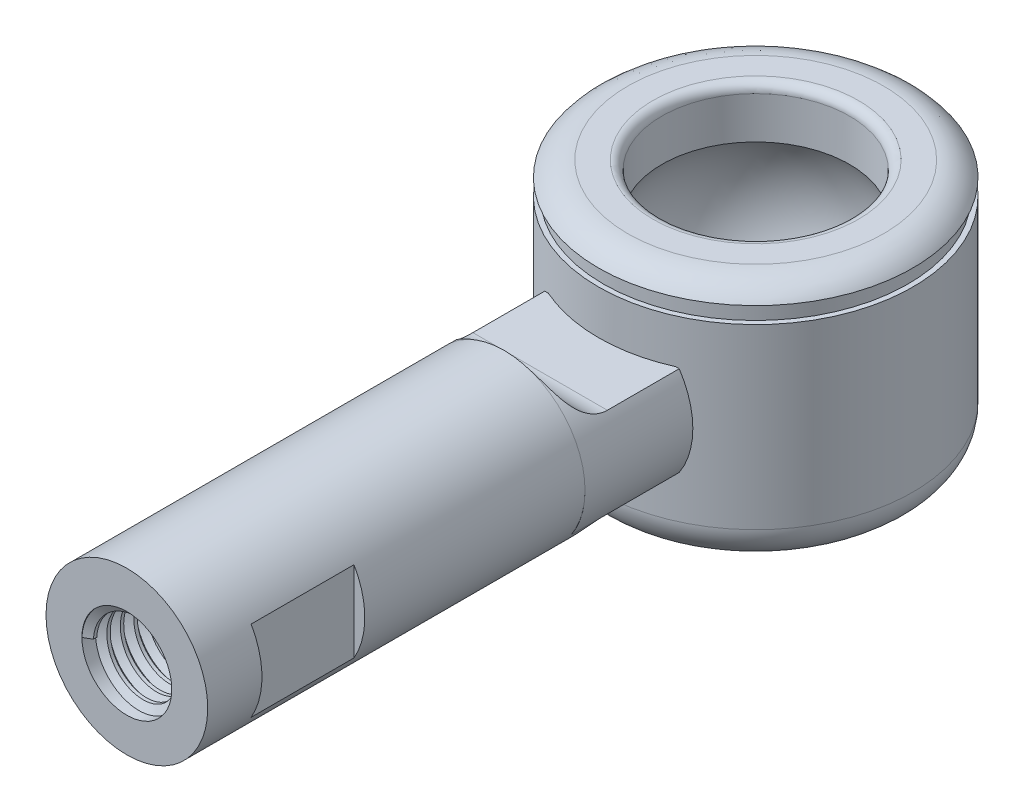
SolidWorks part; units mm, degrees
ref_plane "Front Plane" through (0, 0, 0) normal (0, 0, 1) x (1, 0, 0)
ref_plane "Top Plane" through (0, 0, 0) normal (0, 1, 0) x (1, 0, 0)
ref_plane "Right Plane" through (0, 0, 0) normal (1, 0, 0) x (0, 0, -1)
sketch "Sketch1" plane through (0, 0, 0) normal (0, 0, 1) x (1, 0, 0)
  line L0 (0, 1.3478) -> (0, 1.9842)
  line L1 (10.4493, 27) -> (17.5, 27)
  line L2 (17.5, 27) -> (17.5, 25.3212)
  line L3 (17.5, 0) -> (14.9786, 0)
  line L4 (14.9786, 0) -> (14.9786, 1.3478)
  line L5 (14.9786, 1.3478) -> (0, 1.3478)
  line L6 (0, 26.9842) -> (0, 27)
  line L7 (0, 26.9842) -> (0, 1.3478) construction
  line L10 (17.5, 23.4945) -> (17.5, 0)
  line L11 (17.5, 25.3212) -> (16.9454, 25.3212)
  line L13 (17.5, 23.4945) -> (16.9454, 23.4945)
  line L14 (16.9454, 25.3212) -> (16.9454, 23.4945)
  line L16 (10.4493, 27) -> (10.4493, 21.3443)
  arc A0 (10.4493, 21.3443) -> (0, 1.9842) centre (0, 14.4842) cw
  dimension "D3" = 12.5
  dimension "D2" = 17.5
  dimension "D4" = 1.3478
revolve "Revolve1" add sketch "Sketch1" angle 360 about L7 region at (13.4063, 12.4205, 0)
fillet "Fillet1" radius 4 2 edges at (0, 0, 17.5) (0, 27, 17.5)
ref_plane "Plane1" through (0, 0, 16) normal (0, 0, 1) x (1, 0, 0)
sketch "Sketch2" plane through (0, 0, 16) normal (0, 0, 1) x (1, 0, 0)
  line L0 (0, 23.4945) -> (0, 3.7167)
  line L1 (-7.4833, 18.6056) -> (7.4833, 18.6056)
  line L3 (-7.4833, 8.6056) -> (7.4833, 8.6056)
  line L5 (17.5, 23.4945) -> (-17.5, 23.4945) construction
  line L6 (-17.5, 3.7167) -> (17.5, 3.7167) construction
  arc A0 (-7.4833, 18.6056) -> (-7.4833, 8.6056) centre (0, 13.6056) ccw
  arc A1 (7.4833, 8.6056) -> (7.4833, 18.6056) centre (0, 13.6056) ccw
  point P12 (0, 18.6056)
  dimension "D2" = 18
  dimension "D1" = 10
  dimension "D3" = 5
extrude "Boss-Extrude1" add sketch "Sketch2" along normal blind 12 contours L1 A0 L3 L0 | L3 A1 L1 L0 region at (4.2681, 13.6056, 16) region at (-4.2681, 13.6056, 16)
sketch "Sketch3" plane through (0, 0, 28) normal (0, 0, 1) x (1, 0, 0)
  line L0 (0, 3.7167) -> (0, 23.4945) construction
  circle A0 centre (0, 13.6369) radius 9
  dimension "D1" = 18
extrude "Boss-Extrude2" add sketch "Sketch3" along normal blind 42
fillet "Fillet4" radius 4 2 edges at (0, 8.6056, 28) (0, 18.6056, 28)
sketch "Sketch4" plane through (0, 0, 70) normal (0, 0, 1) x (1, 0, 0)
  line L0 (0, 3.7167) -> (0, 23.4945) construction
  circle A0 centre (0, 13.4627) radius 5
  dimension "D1" = 10
extrude "Cut-Extrude1" cut sketch "Sketch4" against normal blind 42
thread "Thread1" pitch 1.5 method extrude profile "Thread Profile1" start angle 0, offset 0, length 45, pitch 1.5, diameter 10
ref_plane "Plane2" through (-5, 13.4627, 70) normal (0, -1, 0) x (-1, 0, 0)
sketch "Thread Profile1" plane through (-5, 13.4627, 70) normal (0, -1, 0) x (-1, 0, 0)
  line L0 (0, 0) -> (0, 1.5) construction
  line L11 (0, 0) -> (0, 1.3125)
  line L12 (0, 1.3125) -> (-0.8119, 0.8437)
  line L13 (-0.8119, 0.8437) -> (-0.8119, 0.4687)
  line L15 (-0.8119, 0.4687) -> (0, 0)
  line L17 (-0.8119, 0.6562) -> (0, 0.6562) construction
  point P2 (0, 0)
  dimension "Pitch" = 1.5
  dimension "Profile_Angle" = 60
  dimension "Profile_Land" = 0.375
  dimension "Profile_Height" = 0.8119
fillet "Fillet5" radius 1 1 edges at (0, 27, 10.4493)
sketch "Sketch11" plane through (0, 0, 0) normal (0, 1, 0) x (1, 0, 0)
  line L0 (9, -70) -> (9, -28) construction
  line L1 (9, -63.9643) -> (7.7979, -63.9643)
  line L2 (9, -63.9643) -> (9, -52.5136)
  line L3 (9, -52.5136) -> (7.7979, -52.5136)
  line L4 (7.7979, -63.9643) -> (7.7979, -52.5136)
  line L5 (-9, -28) -> (-9, -70) construction
  line L6 (-9, -63.9643) -> (-7.7891, -63.9643)
  line L7 (-9, -63.9643) -> (-9, -52.5136)
  line L8 (-9, -52.5136) -> (-7.7891, -52.5136)
  line L9 (-7.7891, -63.9643) -> (-7.7891, -52.5136)
extrude "Cut-Extrude2" cut sketch "Sketch11" along normal blind 42
